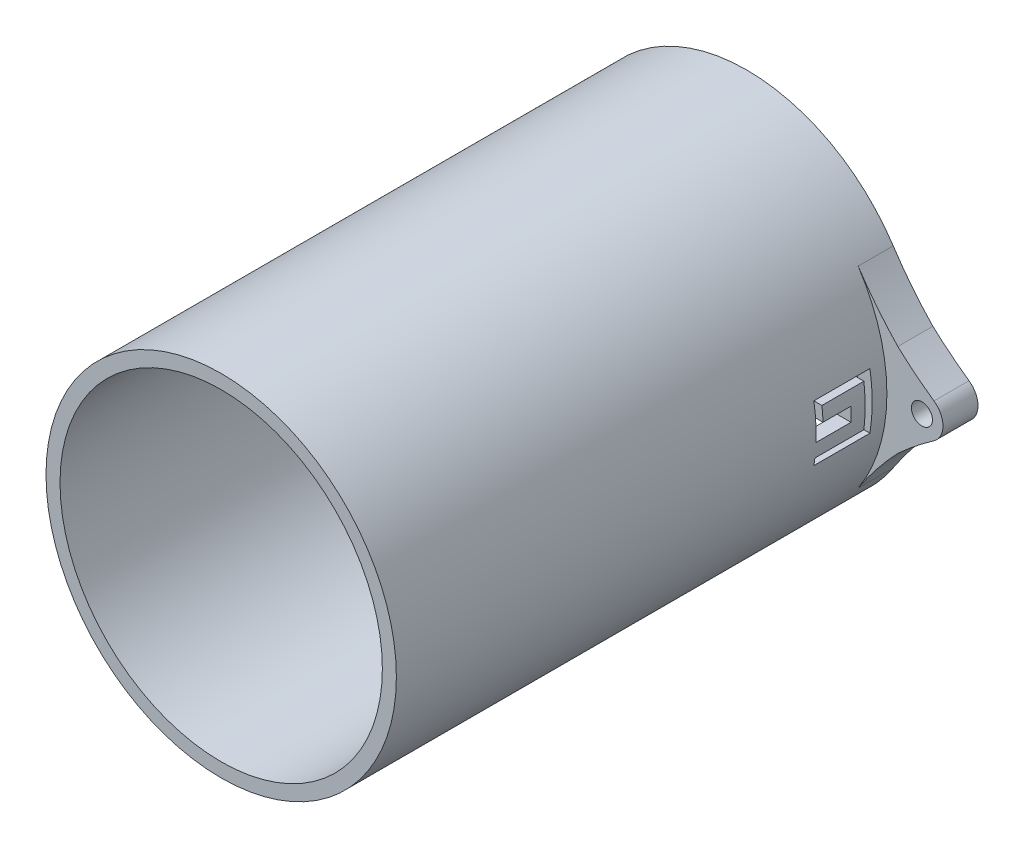
SolidWorks part; units mm, degrees
ref_plane "Plan de face" through (0, 0, 0) normal (0, 0, 1) x (1, 0, 0)
ref_plane "Plan de dessus" through (0, 0, 0) normal (0, 1, 0) x (1, 0, 0)
ref_plane "Plan de droite" through (0, 0, 0) normal (1, 0, 0) x (0, 0, -1)
sketch "Esquisse1" plane through (0, 0, 0) normal (0, 0, 1) x (1, 0, 0)
  line L0 (-30, 3) -> (-22.5479, 10.7977)
  line L7 (-30, -3) -> (-22.5479, -10.7977)
  line L8 (30, 3) -> (22.5479, 10.7977)
  line L9 (30, -3) -> (22.5479, -10.7977)
  circle A0 centre (0, 0) radius 25
  circle A1 centre (0, 0) radius 23
  circle A2 centre (30, 0) radius 1.5
  circle A3 centre (-30, 0) radius 1.5
  circle A4 centre (-30, 0) radius 3
  circle A5 centre (30, 0) radius 3
  dimension "D1" = 50
  dimension "D2" = 46
  dimension "D3" = 3
  dimension "D4" = 3
  dimension "D5" = 6
  dimension "D6" = 6
  dimension "D7" = 30
  dimension "D8" = 30
extrude "Boss.-Extru.1" add sketch "Esquisse1" along normal blind 5 contours A0 A1 | A4 L7 A0 L0 | A5 L8 A0 L9 | A5 A2 | A4 A3 region at (-26.1024, 0, 0) region at (-27.9387, 2.0613, 0) region at (0, 24.2929, 0) region at (26.1024, 0, 0) region at (32.0613, 2.0613, 0)
fillet "Congé1" radius 50 4 edges at (22.5479, -10.7977, 2.5) (22.5479, 10.7977, 2.5) (-22.5479, 10.7977, 2.5) (-22.5479, -10.7977, 2.5)
fillet "Congé2" radius 50 4 edges at (30, -3, 2.5) (30, 3, 2.5) (-30, 3, 2.5) (-30, -3, 2.5)
sketch "Esquisse2" plane through (0, 0, 5) normal (0, 0, 1) x (1, 0, 0)
  circle A0 centre (0, 0) radius 23
  circle A1 centre (0, 0) radius 25
extrude "Boss.-Extru.2" add sketch "Esquisse2" along normal blind 70
sketch "Esquisse3" plane through (0, 0, 0) normal (1, 0, 0) x (0, 0, -1)
  line L0 (-5, 13.7158) -> (-5, -13.7158) construction
  line L1 (-15.0969, 4) -> (-7.0969, 4)
  line L2 (-15.0969, 4) -> (-15.0969, -4)
  line L3 (-15.0969, -4) -> (-7.0969, -4)
  line L4 (-7.0969, 4) -> (-7.0969, -4)
  line L5 (-15.0969, 4) -> (-7.0969, -4) construction
  line L6 (-15.0969, -4) -> (-7.0969, 4) construction
  line L7 (-15.0969, 4) -> (-7.0969, 4)
  line L8 (-15.0969, -3) -> (-8.0969, -3)
  line L9 (-15.0969, -3) -> (-15.0969, -1)
  line L10 (-15.0969, -1) -> (-8.0969, -1)
  line L11 (-8.0969, -3) -> (-8.0969, -1)
  line L12 (-8.0969, -1) -> (-10.0969, -1)
  line L13 (-8.0969, -1) -> (-8.0969, 3)
  line L14 (-8.0969, 3) -> (-10.0969, 3)
  line L15 (-10.0969, -1) -> (-10.0969, 3)
  line L16 (-10.0969, 3) -> (-14.0969, 3)
  line L17 (-10.0969, 3) -> (-10.0969, 1)
  line L18 (-10.0969, 1) -> (-14.0969, 1)
  line L19 (-14.0969, 3) -> (-14.0969, 1)
  line L20 (-7.0969, -4) -> (-15.0969, -4)
  line L21 (-15.0969, -3) -> (-8.0969, -3)
  line L22 (-8.0969, 3) -> (-14.0969, 3)
  line L23 (-14.0969, 1) -> (-10.0969, 1)
  line L24 (-10.0969, 1) -> (-10.0644, 1.0402)
  line L25 (-10.0969, -1) -> (-15.0969, -1)
  point P0 (-11.0969, 0)
  dimension "D1" = 8
  dimension "D2" = 8
  dimension "D3" = 2.0969
  dimension "D4" = 2
  dimension "D5" = 7
  dimension "D6" = 1
  dimension "D7" = 2
  dimension "D8" = 4
  dimension "D9" = 2
  dimension "D10" = 1
extrude "Enlèv. mat.-Extru.1" cut sketch "Esquisse3" against normal through all both and the other way through all contours L19 L16 L14 L13 L11 L8 L2 L3 L4 L1 L10 L15 L18 region at (0, 0.1176, 11.1263)
